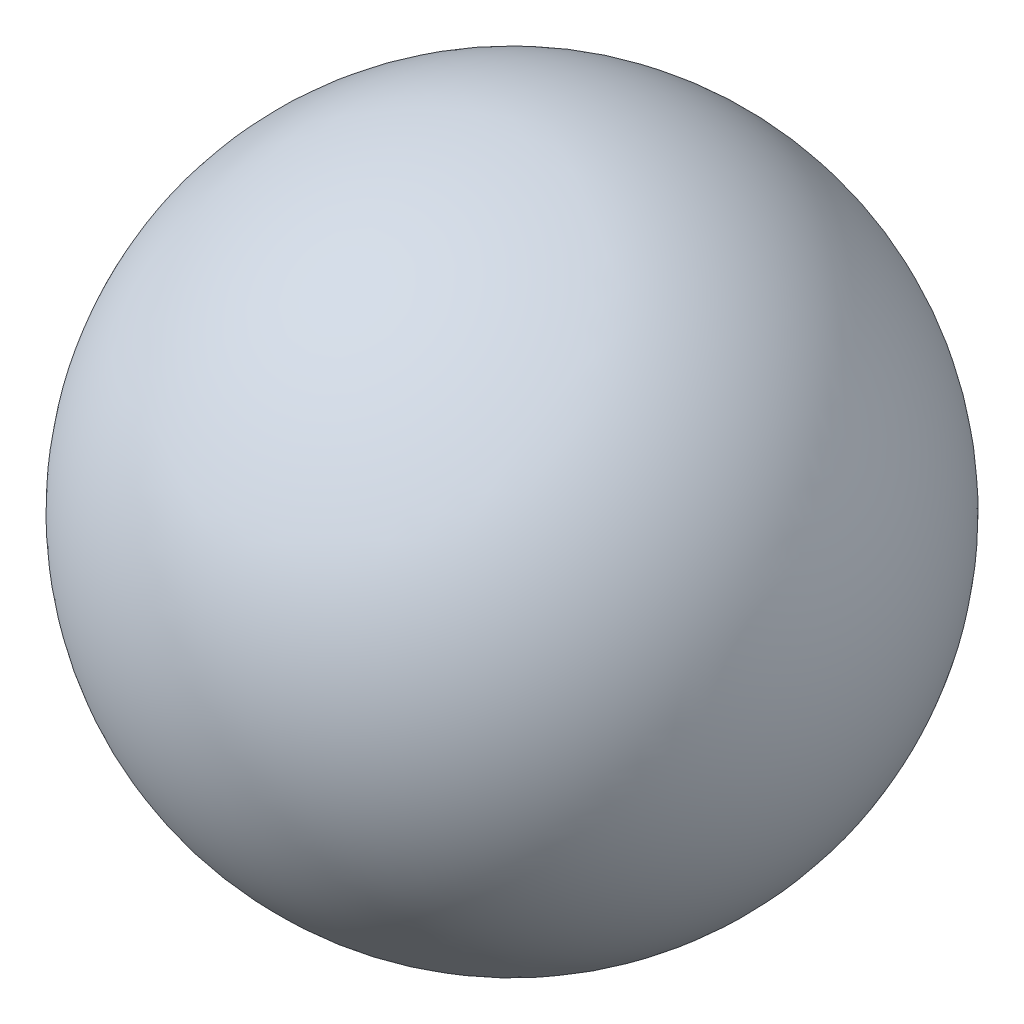
SolidWorks part; units mm, degrees
ref_plane "Front Plane" through (0, 0, 0) normal (0, 0, 1) x (1, 0, 0)
ref_plane "Top Plane" through (0, 0, 0) normal (0, 1, 0) x (1, 0, 0)
ref_plane "Right Plane" through (0, 0, 0) normal (1, 0, 0) x (0, 0, -1)
sketch "Sketch1" plane through (0, 0, 0) normal (0, 1, 0) x (1, 0, 0)
  line L0 (-20, 0) -> (20, 0) construction
  circle A0 centre (0, 0) radius 20
  dimension "D1" = 40
revolve "Revolve2" add sketch "Sketch1" angle 360 about L0 region at (0, 0, 8.4883)
